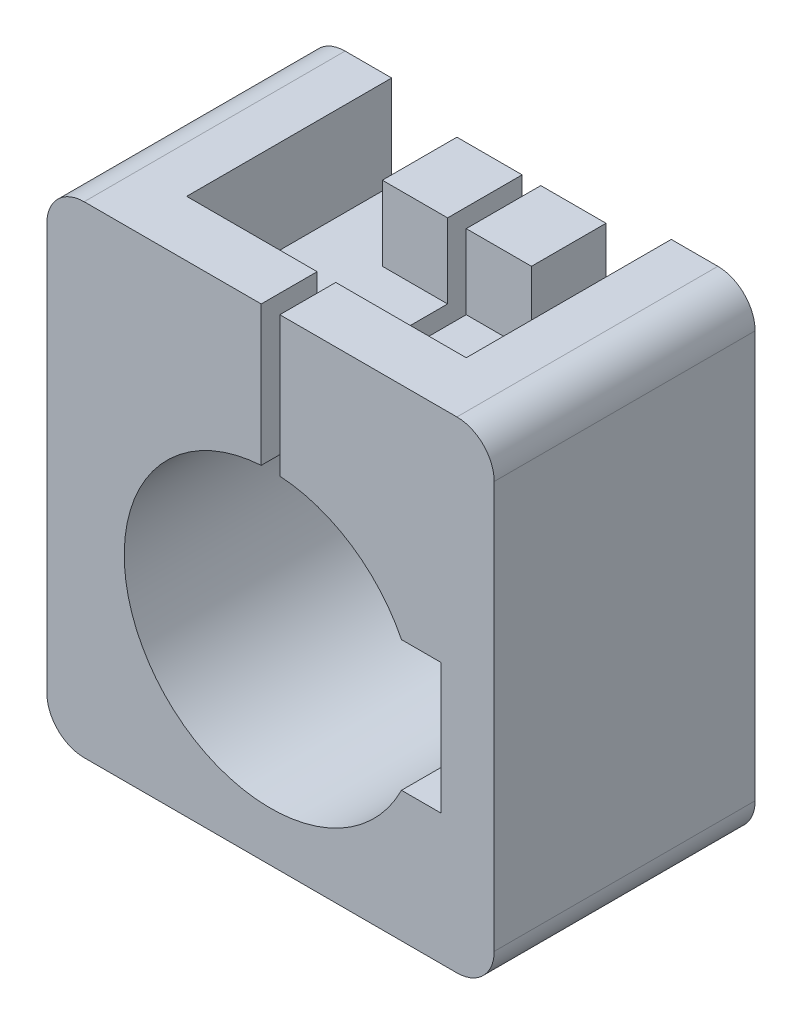
SolidWorks part; units mm, degrees
ref_plane "Alzado" through (0, 0, 0) normal (0, 0, 1) x (1, 0, 0)
ref_plane "Planta" through (0, 0, 0) normal (0, 1, 0) x (1, 0, 0)
ref_plane "Vista lateral" through (0, 0, 0) normal (1, 0, 0) x (0, 0, -1)
sketch "Croquis1" plane through (0, 0, 0) normal (0, 0, 1) x (1, 0, 0)
  line L7 (-12, -10.5) -> (12, -10.5)
  line L8 (9.15, 3.5) -> (7.0266, 3.5)
  line L9 (9.15, 3.5) -> (9.15, -3.5)
  line L10 (9.15, -3.5) -> (7.0266, -3.5)
  line L11 (7.0266, 3.5) -> (7.0266, -3.5) construction
  line L12 (-12, -10.5) -> (-12, 10.3341)
  line L13 (-12, 10.3341) -> (-0.5, 10.3341)
  line L14 (12, 10.3341) -> (12, -10.5)
  line L15 (0.5, 10.3341) -> (12, 10.3341)
  line L16 (-0.5, 10.3341) -> (0.5, 10.3341) construction
  line L17 (-0.5, 10.3341) -> (-0.5, 7.8341)
  line L18 (-0.5, 7.8341) -> (0.5, 7.8341) construction
  line L19 (0.5, 10.3341) -> (0.5, 7.8341)
  arc A2 (7.0266, 3.5) -> (0.5, 7.8341) centre (0, 0) ccw
  arc A3 (-0.5, 7.8341) -> (7.0266, -3.5) centre (0, 0) ccw
  point P7 (-7.85, 0)
  point P8 (7.0266, 0)
  point P11 (0, -10.5)
  point P17 (0, 10.3341)
  dimension "D1" = 15.7
  dimension "D2" = 17
  dimension "D3" = 7
  dimension "D4" = 10.5
  dimension "D5" = 24
  dimension "D6" = 2.5
  dimension "D7" = 1
extrude "Saliente-Extruir1" add sketch "Croquis1" along normal mid plane 14
sketch "Croquis2" plane through (0, 0, -7) normal (0, 0, 1) x (1, 0, 0)
  line L0 (0.5, 14.3341) -> (-0.5, 14.3341) construction
  line L1 (0.5, 10.3341) -> (4, 10.3341)
  line L2 (0.5, 10.3341) -> (0.5, 14.3341)
  line L3 (0.5, 14.3341) -> (4, 14.3341)
  line L4 (4, 10.3341) -> (4, 14.3341)
  line L5 (-0.5, 10.3341) -> (-4, 10.3341)
  line L6 (-0.5, 10.3341) -> (-0.5, 14.3341)
  line L7 (-0.5, 14.3341) -> (-4, 14.3341)
  line L8 (-4, 10.3341) -> (-4, 14.3341)
  dimension "D1" = 4
  dimension "D2" = 3.5
extrude "Saliente-Extruir2" add sketch "Croquis2" along normal blind 4
sketch "Croquis3" plane through (0, 0, 7) normal (0, 0, -1) x (-1, 0, 0)
  line L0 (-12, -10.5) -> (-12, 10.3341) construction
  line L1 (-0.5, 10.3341) -> (-12, 10.3341)
  line L2 (-0.5, 10.3341) -> (-0.5, 15.3341)
  line L3 (-0.5, 15.3341) -> (-12, 15.3341)
  line L4 (-12, 10.3341) -> (-12, 15.3341)
  line L5 (0.5, 10.3341) -> (12, 10.3341)
  line L6 (0.5, 10.3341) -> (0.5, 15.3341)
  line L7 (0.5, 15.3341) -> (12, 15.3341)
  line L8 (12, 10.3341) -> (12, 15.3341)
  line L9 (0.5, 10.3341) -> (-0.5, 10.3341) construction
  line L10 (-0.5, 10.3341) -> (-4, 10.3341) construction
  line L11 (0.5, 10.3341) -> (0.5, 14.3341) construction
  line L12 (-0.5, 14.3341) -> (-0.5, 10.3341) construction
  dimension "D2" = 5
extrude "Saliente-Extruir3" add sketch "Croquis3" along normal blind 3
sketch "Croquis4" plane through (0, 0, 0) normal (0, 0, 1) x (1, 0, 0)
  line L0 (-0.5, 10.3341) -> (-12, 10.3341) construction
  line L1 (-7.5, 10.3341) -> (7.5, 10.3341) construction
  line L2 (-7.5, 10.3341) -> (-7.5, 15.3341) construction
  line L3 (-7.5, 15.3341) -> (7.5, 15.3341) construction
  line L4 (7.5, 10.3341) -> (7.5, 15.3341) construction
  line L5 (-12, 15.3341) -> (-0.5, 15.3341) construction
  line L7 (-12, 15.3341) -> (-7.5, 15.3341)
  line L8 (-12, 15.3341) -> (-12, 10.3341)
  line L9 (-12, 10.3341) -> (-7.5, 10.3341)
  line L10 (-7.5, 15.3341) -> (-7.5, 10.3341)
  line L11 (7.5, 15.3341) -> (12, 15.3341)
  line L12 (7.5, 15.3341) -> (7.5, 10.3341)
  line L13 (7.5, 10.3341) -> (12, 10.3341)
  line L14 (12, 15.3341) -> (12, 10.3341)
  point P6 (0, 15.3341)
  dimension "D1" = 15
extrude "Saliente-Extruir4" add sketch "Croquis4" along normal up to surface (4 mm away) and the other way up to surface (7 mm away) up to face at (6.25, 12.8341, 4) other way up to face at (1.4456, 5.4815, -7)
fillet "Redondeo3" radius 2 4 edges at (12, -10.5, 0) (-12, -10.5, 0) (12, 15.3341, 0) (-12, 15.3341, 0)
